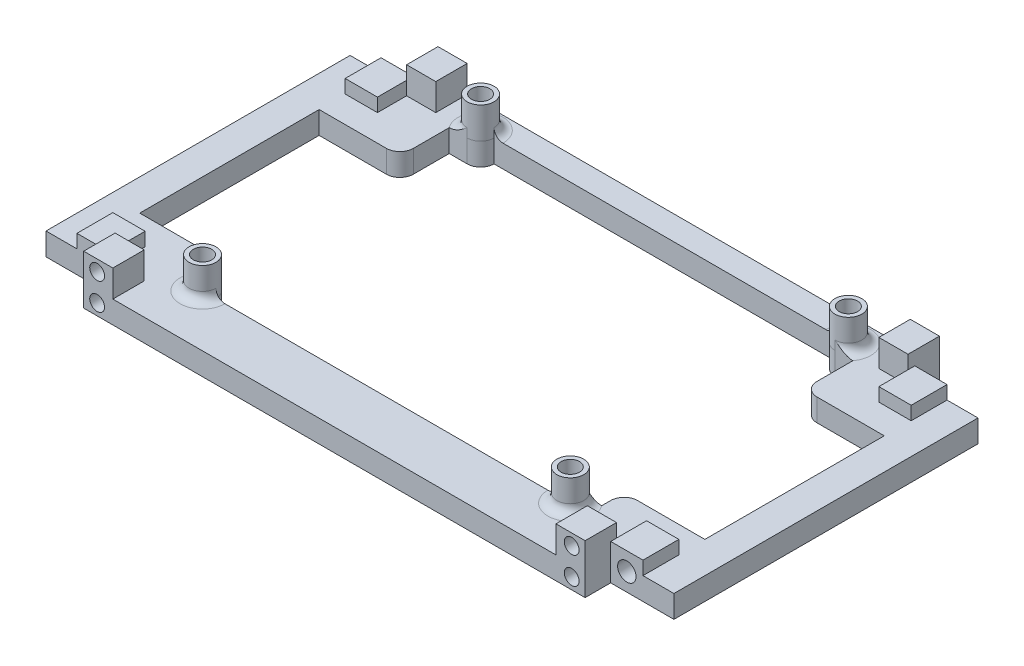
SolidWorks part; units mm, degrees
ref_plane "Front Plane" through (0, 0, 0) normal (0, 0, 1) x (1, 0, 0)
ref_plane "Top Plane" through (0, 0, 0) normal (0, 1, 0) x (1, 0, 0)
ref_plane "Right Plane" through (0, 0, 0) normal (1, 0, 0) x (0, 0, -1)
sketch "Sketch1" plane through (0, 0, 0) normal (0, 1, 0) x (1, 0, 0)
  line L0 (-70, -33.9) -> (-70, 33.9)
  line L1 (-70, -41) -> (70, -41) construction
  line L2 (-70, -41) -> (-70, 41) construction
  line L3 (-70, 41) -> (70, 41) construction
  line L4 (70, -41) -> (70, 41) construction
  line L5 (-70, -41) -> (70, 41) construction
  line L6 (-70, 41) -> (70, -41) construction
  line L7 (-70, 33.9) -> (-55.9, 33.9)
  line L8 (-55.9, 33.9) -> (-55.9, 41)
  line L9 (-55.9, 41) -> (55.9, 41)
  line L10 (55.9, 41) -> (55.9, 33.9)
  line L11 (55.9, 33.9) -> (70, 33.9)
  line L12 (70, 33.9) -> (70, -33.9)
  line L13 (70, -33.9) -> (55.9, -33.9)
  line L14 (55.9, -33.9) -> (55.9, -41)
  line L15 (55.9, -41) -> (-55.9, -41)
  line L16 (-55.9, -41) -> (-55.9, -33.9)
  line L17 (-55.9, -33.9) -> (-70, -33.9)
  point P0 (0, 0)
  dimension "D1" = 140
  dimension "D2" = 82
  dimension "D3" = 7.1
  dimension "D4" = 14.1
extrude "Boss-Extrude1" add sketch "Sketch1" along normal blind 5
sketch "Sketch3" plane through (0, 5, 0) normal (0, 1, 0) x (1, 0, 0)
  line L1 (-41, 34) -> (41, 34) construction
  line L2 (-41, 34) -> (-41, -28) construction
  line L3 (-41, -28) -> (41, -28) construction
  line L4 (41, 34) -> (41, -28) construction
  line L5 (-41, 34) -> (41, -28) construction
  line L6 (-41, -28) -> (41, 34) construction
  circle A0 centre (-41, -28) radius 3
  circle A1 centre (41, -28) radius 3
  circle A2 centre (41, 34) radius 3
  circle A3 centre (-41, 34) radius 3
  point P0 (0, 3)
  dimension "D4" = 6
  dimension "D1" = 82
  dimension "D2" = 62
  dimension "D3" = 3
sketch "Sketch2" plane through (0, 5, 0) normal (0, 1, 0) x (1, 0, 0)
  line L0 (-41, 31) -> (-38, 31)
  line L5 (-38, -28) -> (38, -28)
  line L6 (-41, -25) -> (-41, 31)
  line L7 (-38, 34) -> (38, 34)
  line L8 (41, -25) -> (41, 31)
  line L9 (-41, -28) -> (41, 34) construction
  line L10 (-41, 34) -> (41, -28) construction
  line L11 (-38, 31) -> (-38, 34)
  line L12 (38, 34) -> (38, 31)
  line L13 (38, 31) -> (41, 31)
  line L14 (41, -25) -> (38, -25)
  line L15 (38, -25) -> (38, -28)
  line L16 (-38, -28) -> (-38, -25)
  line L17 (-38, -25) -> (-41, -25)
  line L18 (41, -28) -> (-41, -28) construction
  line L19 (-41, -28) -> (-41, 34) construction
  line L20 (-41, 34) -> (41, 34) construction
  line L21 (41, 34) -> (41, -28) construction
  point P0 (0, 0)
  point P1 (0, 3)
  dimension "D1" = 3
extrude "Cut-Extrude1" cut sketch "Sketch2" against normal through all
extrude "Boss-Extrude2" add sketch "Sketch3" along normal blind 7
sketch "Sketch4" plane through (0, 12, 0) normal (0, 1, 0) x (1, 0, 0)
  circle A0 centre (-41, 34) radius 2.05
  circle A1 centre (41, 34) radius 2.05
  circle A2 centre (41, -28) radius 2.05
  circle A3 centre (-41, -28) radius 2.05
  dimension "D1" = 4.1
extrude "Cut-Extrude2" cut sketch "Sketch4" against normal through all and the other way through all
sketch "Sketch5" plane through (0, 5, 0) normal (0, 1, 0) x (1, 0, 0)
  line L0 (-41, -25) -> (-38, -25) construction
  line L1 (-41, 31) -> (-53, 31)
  line L2 (-41, 31) -> (-41, -25)
  line L3 (-41, -25) -> (-53, -25)
  line L4 (-53, 31) -> (-53, -25)
  line L5 (0, 34) -> (0, -28) construction
  line L6 (38, 34) -> (-38, 34) construction
  line L7 (-38, -28) -> (38, -28) construction
  line L8 (53, 31) -> (53, -25)
  line L9 (41, -25) -> (53, -25)
  line L10 (41, 31) -> (41, -25)
  line L11 (41, 31) -> (53, 31)
  dimension "D1" = 12
extrude "Cut-Extrude3" cut sketch "Sketch5" against normal through all
fillet "Fillet1" radius 3 4 edges at (38, 2.5, 25) (-38, 2.5, 25) (38, 2.5, -31) (-38, 2.5, -31)
sketch "Sketch6" plane through (0, 5, 0) normal (0, 1, 0) x (1, 0, 0)
  line L0 (38, 34) -> (-38, 34) construction
  line L1 (-25, 34) -> (25, 34)
  line L2 (-25, 34) -> (-25, 28)
  line L3 (-25, 28) -> (25, 28)
  line L4 (25, 34) -> (25, 28)
  line L5 (0, -28) -> (0, -41) construction
  line L6 (-38, -28) -> (38, -28) construction
  line L7 (-55.9, -41) -> (55.9, -41) construction
  line L8 (0, 28) -> (0, 41) construction
  line L9 (55.9, 41) -> (-55.9, 41) construction
  point P6 (0, 28)
  dimension "D1" = 50
sketch "Sketch7" plane through (0, 5, 0) normal (0, 1, 0) x (1, 0, 0)
  line L0 (0, 41) -> (0, -41) construction
  line L1 (55.9, 33.9) -> (63.1, 33.9)
  line L2 (55.9, 33.9) -> (55.9, 25.9)
  line L3 (55.9, 25.9) -> (63.1, 25.9)
  line L4 (63.1, 33.9) -> (63.1, 25.9)
  line L5 (55.9, 41) -> (-55.9, 41) construction
  line L6 (-55.9, -41) -> (55.9, -41) construction
  line L7 (-70, 0) -> (70, 0) construction
  line L8 (-70, 33.9) -> (-70, -33.9) construction
  line L9 (70, -33.9) -> (70, 33.9) construction
  dimension "D1" = 7.2
  dimension "D2" = 8
extrude "Boss-Extrude3" add sketch "Sketch7" along normal blind 3
sketch "Sketch8" plane through (0, 0, -33.9) normal (0, 0, -1) x (-1, 0, 0)
  line L0 (-63.1, 8) -> (-55.9, 0) construction
  circle A0 centre (-59.5, 4) radius 2.05
  dimension "D1" = 4.1
extrude "Cut-Extrude5" cut sketch "Sketch8" against normal blind 6
mirror "Mirror3" about plane through (0, 0, 0) normal (1, 0, 0) of "Cut-Extrude5", "Boss-Extrude3"
mirror "Mirror4" about plane through (0, 0, 0) normal (0, 0, 1) of "Mirror3"
sketch "Sketch10" plane through (0, 5, 0) normal (0, 1, 0) x (1, 0, 0)
  line L0 (55.9, 33.9) -> (55.9, 41) construction
  line L1 (-55.9, 41) -> (55.9, 41)
  line L2 (-55.9, 41) -> (-55.9, 40)
  line L3 (-55.9, 40) -> (55.9, 40)
  line L4 (55.9, 41) -> (55.9, 40)
  line L5 (-55.9, -33.9) -> (-55.9, -41) construction
  line L6 (55.9, -41) -> (-55.9, -41)
  line L7 (55.9, -41) -> (55.9, -40)
  line L8 (55.9, -40) -> (-55.9, -40)
  line L9 (-55.9, -41) -> (-55.9, -40)
  dimension "D1" = 1
  dimension "D2" = 1
extrude "Cut-Extrude7" cut sketch "Sketch10" against normal through all
fillet "Fillet5" radius 2 4 edges at (43.1213, 5, -36.1213) (43.1213, 5, 30.1213) (-43.1213, 5, 30.1213) (-43.1213, 5, -36.1213)
sketch "Sketch11" plane through (0, 5, 0) normal (0, 1, 0) x (1, 0, 0)
  line L1 (53, -25) -> (45, -25)
  line L2 (53, -25) -> (53, 31)
  line L3 (53, 31) -> (45, 31)
  line L4 (45, -25) -> (45, 31)
  line L5 (-45, -25) -> (-53, -25)
  line L6 (-45, -25) -> (-45, 31)
  line L7 (-45, 31) -> (-53, 31)
  line L8 (-53, -25) -> (-53, 31)
extrude "Boss-Extrude4" add sketch "Sketch11" against normal up to surface (5 mm away) up to face at (0, 0, 0)
sketch "Sketch12" plane through (0, 5, 0) normal (0, 1, 0) x (1, 0, 0)
  line L0 (45, 31) -> (45, -25) construction
  line L1 (45, 20) -> (63, 20)
  line L2 (45, 20) -> (45, -20)
  line L3 (45, -20) -> (63, -20)
  line L4 (63, 20) -> (63, -20)
  line L5 (70, -33.9) -> (70, 33.9) construction
  point P6 (63, 0)
  point P9 (70, 0)
  dimension "D1" = 18
  dimension "D2" = 40
extrude "Cut-Extrude8" cut sketch "Sketch12" against normal through all and the other way through all
mirror "Mirror7" about plane through (0, 0, 0) normal (1, 0, 0) of "Cut-Extrude8"
fillet "Fillet6" radius 3 4 edges at (45, 2.5, -20) (45, 2.5, 20) (-45, 2.5, -20) (-45, 2.5, 20)
sketch "Sketch13" plane through (0, 5, 0) normal (0, 1, 0) x (1, 0, 0)
  line L0 (55.9, 33.9) -> (55.9, 40) construction
  line L1 (-55.9, 40) -> (55.9, 40)
  line L2 (-55.9, 40) -> (-55.9, 39.4)
  line L3 (-55.9, 39.4) -> (55.9, 39.4)
  line L4 (55.9, 40) -> (55.9, 39.4)
  line L5 (-55.9, -33.9) -> (-55.9, -40) construction
  line L6 (55.9, -40) -> (-55.9, -40)
  line L7 (55.9, -40) -> (55.9, -39.6)
  line L8 (55.9, -39.6) -> (-55.9, -39.6)
  line L9 (-55.9, -40) -> (-55.9, -39.6)
  dimension "D1" = 0.6
  dimension "D2" = 0.4
extrude "Cut-Extrude9" cut sketch "Sketch13" against normal through all both and the other way through all
sketch "Sketch14" plane through (0, 5, 0) normal (0, 1, 0) x (1, 0, 0)
  line L1 (-55.9, -39.6) -> (-49.4, -39.6)
  line L2 (-55.9, -39.6) -> (-55.9, -32.6)
  line L3 (-55.9, -32.6) -> (-49.4, -32.6)
  line L4 (-49.4, -39.6) -> (-49.4, -32.6)
  line L5 (-55.9, 39.4) -> (-49.4, 39.4)
  line L6 (-55.9, 39.4) -> (-55.9, 32.4)
  line L7 (-55.9, 32.4) -> (-49.4, 32.4)
  line L8 (-49.4, 39.4) -> (-49.4, 32.4)
  dimension "D1" = 6.5
  dimension "D2" = 7
extrude "Boss-Extrude5" add sketch "Sketch14" along normal blind 6
sketch "Sketch15" plane through (0, 0, 39.6) normal (0, 0, 1) x (1, 0, 0)
  line L0 (-49.4, 5) -> (-49.4, 0) construction
  line L1 (55.9, 0) -> (-55.9, 0) construction
  line L3 (-55.9, 0) -> (-55.9, 11) construction
  circle A0 centre (-52.9, 2.5) radius 1.65
  circle A1 centre (-52.9, 8.5) radius 1.65
  point P4 (-49.4, 2.5)
  dimension "D1" = 3.3
  dimension "D2" = 3
  dimension "D3" = 6
extrude "Cut-Extrude10" cut sketch "Sketch15" against normal blind 6
sketch "Sketch16" plane through (0, 0, -39.4) normal (0, 0, -1) x (-1, 0, 0)
  circle A0 centre (52.9, 8.5) radius 1.65 construction
  circle A1 centre (52.9, 2.5) radius 1.65 construction
  circle A2 centre (52.9, 8.5) radius 1.65
  circle A3 centre (52.9, 2.5) radius 1.65
extrude "Cut-Extrude11" cut sketch "Sketch16" against normal blind 6
mirror "Mirror8" about plane through (0, 0, 0) normal (1, 0, 0) of "Cut-Extrude10", "Cut-Extrude11", "Boss-Extrude5"
